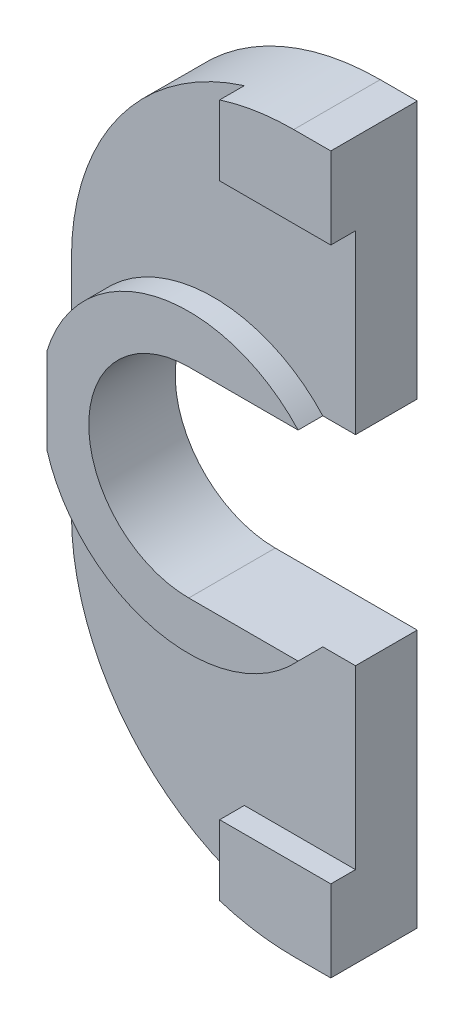
SolidWorks part; units mm, degrees
ref_plane "Front Plane" through (0, 0, 0) normal (0, 0, 1) x (1, 0, 0)
ref_plane "Top Plane" through (0, 0, 0) normal (0, 1, 0) x (1, 0, 0)
ref_plane "Right Plane" through (0, 0, 0) normal (1, 0, 0) x (0, 0, -1)
sketch "Sketch2" plane through (0, 0, 0) normal (0, 0, 1) x (1, 0, 0)
  line L0 (0, 4.05) -> (5.75, 4.05)
  line L1 (5.75, -14.5) -> (4.25, -14.5)
  line L2 (5.75, -14.5) -> (5.75, -4.05)
  line L3 (5.75, 14.5) -> (4.25, 14.5)
  line L4 (-5.75, -4.5) -> (-5.75, 4.5)
  line L5 (5.75, -14.5) -> (1.4929, -3.7648) construction
  line L6 (5.75, 14.5) -> (1.4929, 3.7648) construction
  line L7 (0, -4.05) -> (5.75, -4.05)
  line L8 (5.75, 4.05) -> (5.75, 14.5)
  line L9 (0, 0) -> (-5.75, -14.5) construction
  line L10 (0, 0) -> (-5.75, 14.5) construction
  arc A0 (0, 4.05) -> (0, -4.05) centre (0, 0) ccw
  arc A1 (4.25, -14.5) -> (-5.75, -4.5) centre (4.25, -4.5) cw
  arc A2 (-5.75, 4.5) -> (4.25, 14.5) centre (4.25, 4.5) cw
  point P0 (0, 0)
  dimension "D3" = 8.1
  dimension "D4" = 10
  dimension "D1" = 11.5
  dimension "D2" = 29
extrude "Boss-Extrude1" add sketch "Sketch2" along normal blind 2.5
sketch "Sketch3" plane through (0, 0, 2.5) normal (0, 0, 1) x (1, 0, 0)
  line L0 (0, 4.05) -> (5.75, 4.05) construction
  line L1 (5.75, -4.05) -> (0, -4.05) construction
  line L2 (0, 4.05) -> (4.4269, 4.05)
  line L3 (4.4269, -4.05) -> (0, -4.05)
  line L4 (-5.75, 4.5) -> (-5.75, -4.5) construction
  line L5 (-5.75, 1.7139) -> (-5.75, -1.7139)
  arc A0 (0, 4.05) -> (0, -4.05) centre (0, 0) ccw construction
  arc A1 (0, 4.05) -> (0, -4.05) centre (0, 0) ccw
  arc A2 (4.4269, 4.05) -> (-5.75, 1.7139) centre (0, 0) ccw
  arc A3 (-5.75, -1.7139) -> (4.4269, -4.05) centre (0, 0) ccw
  dimension "D1" = 12
extrude "Boss-Extrude2" add sketch "Sketch3" along normal blind 1
sketch "Sketch4" plane through (0, 0, 2.5) normal (0, 0, 1) x (1, 0, 0)
  line L0 (5.75, 11.2) -> (1.25, 11.2)
  line L1 (1.25, 11.2) -> (1.25, 14.0394)
  line L4 (4.4269, 4.05) -> (5.75, 4.05)
  line L5 (5.75, 4.05) -> (5.75, 14.5)
  line L6 (5.75, 14.5) -> (4.25, 14.5)
  line L7 (-5.75, 4.5) -> (-5.75, 1.7139)
  line L8 (4.4269, 4.05) -> (5.75, 4.05)
  line L9 (5.75, 4.05) -> (5.75, 14.5)
  line L10 (5.75, 14.5) -> (4.25, 14.5)
  line L11 (-5.75, 4.5) -> (-5.75, 1.7139)
  arc A2 (4.4269, 4.05) -> (-5.75, 1.7139) centre (0, 0) ccw
  arc A3 (4.25, 14.5) -> (-5.75, 4.5) centre (4.25, 4.5) ccw
  arc A4 (4.4269, 4.05) -> (-5.75, 1.7139) centre (0, 0) ccw
  arc A5 (4.25, 14.5) -> (-5.75, 4.5) centre (4.25, 4.5) ccw
  line M9 (5.75, 4.05) -> (5.75, 14.5)
  line M10 (5.75, 14.5) -> (4.25, 14.5)
  arc M11 (4.25, 14.5) -> (-5.75, 4.5) centre (4.25, 4.5) ccw
  dimension "D2" = 4.5
  dimension "D3" = 3.3
  dimension "D1" = 0
extrude "Boss-Extrude3" add sketch "Sketch4" along normal blind 1 contours L1 L0 M9 M10 M11 region at (3.5477, 12.8021, 2.5)
mirror "Mirror1" about plane through (0, 0, 0) normal (0, 1, 0) of "Boss-Extrude3"
